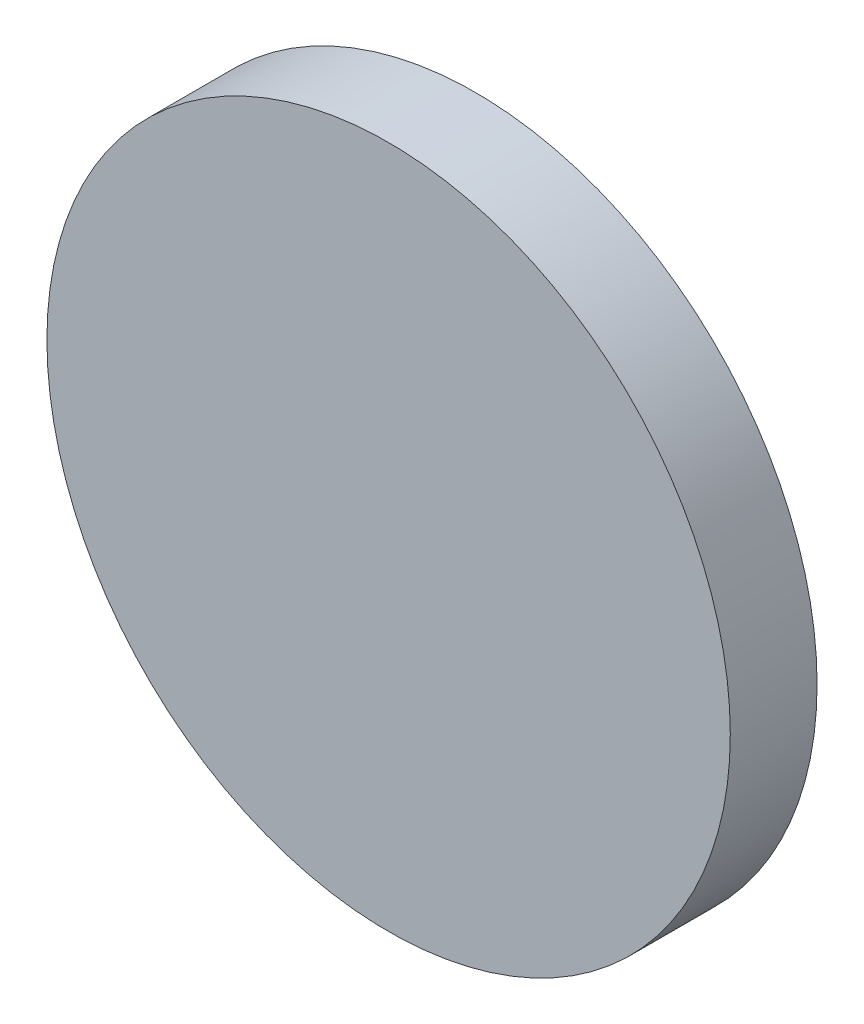
SolidWorks part; units mm, degrees
material "ABS"
ref_plane "Front Plane" through (0, 0, 0) normal (0, 0, 1) x (1, 0, 0)
ref_plane "Top Plane" through (0, 0, 0) normal (0, 1, 0) x (1, 0, 0)
ref_plane "Right Plane" through (0, 0, 0) normal (1, 0, 0) x (0, 0, -1)
sketch "Sketch1" plane through (0, 0, 0) normal (0, 0, 1) x (1, 0, 0)
  circle A0 centre (0, 0) radius 25
  dimension "D1" = 50
extrude "Boss-Extrude1" add sketch "Sketch1" along normal blind 6.35 contours A0
